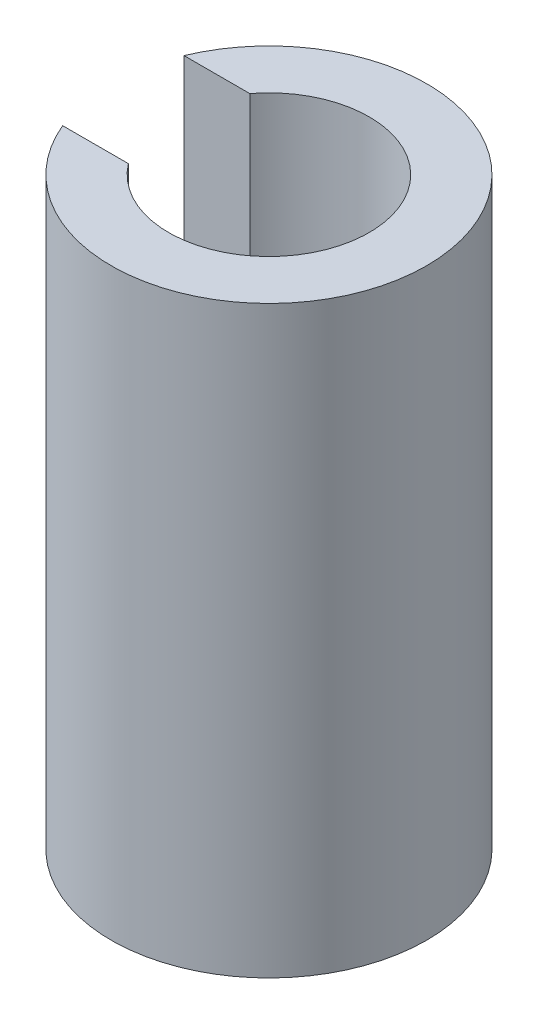
SolidWorks part; units mm, degrees
ref_plane "前基準面" through (0, 0, 0) normal (0, 0, 1) x (1, 0, 0)
ref_plane "上基準面" through (0, 0, 0) normal (0, 1, 0) x (1, 0, 0)
ref_plane "右基準面" through (0, 0, 0) normal (1, 0, 0) x (0, 0, -1)
ref_axis "基準軸1" through (0, -55, 0) along (0, 1, 0)
ref_axis "基準軸2" through (-88.99, 0, 0) along (1, 0, 0)
ref_axis "基準軸3" through (0, 0, 55) along (0, 0, -1)
sketch "草圖1" plane through (0, 0, 0) normal (0, 1, 0) x (1, 0, 0)
  circle A0 centre (0, 0) radius 2.575
  circle A1 centre (0, 0) radius 4.05
  dimension "D1" = 5.15
  dimension "D2" = 8.1
extrude "填料-伸長1" add sketch "草圖1" along normal blind 15
sketch "草圖2" plane through (0, 15, 0) normal (0, 1, 0) x (1, 0, 0)
  line L1 (-4.05, -1.5582) -> (-2.05, -1.5582)
  line L2 (-4.05, -1.5582) -> (-4.05, 1.5582)
  line L3 (-4.05, 1.5582) -> (-2.05, 1.5582)
  line L4 (-2.05, -1.5582) -> (-2.05, 1.5582)
  line L5 (-55, 0) -> (55, 0) construction
  circle A0 centre (0, 0) radius 4.05 construction
  circle A1 centre (0, 0) radius 2.575 construction
  point P4 (-2.05, 0)
  dimension "D1" = 2
extrude "除料-伸長1" cut sketch "草圖2" against normal blind 15
sketch "草圖3" plane through (0, 0, 0) normal (0, -1, 0) x (1, 0, 0)
  line L0 (1.1456, 0.5) -> (2.526, 0.5)
  line L1 (1.1456, -0.5) -> (2.526, -0.5)
  line L2 (4.2835, 0) -> (-4.2835, 0) construction
  arc A0 (1.1456, 0.5) -> (1.1456, -0.5) centre (0, 0) ccw
  arc A1 (-2.05, -1.5582) -> (-2.05, 1.5582) centre (0, 0) ccw construction
  arc A2 (2.526, -0.5) -> (2.526, 0.5) centre (0, 0) ccw
  dimension "D1" = 2.5
  dimension "D2" = 0.5
  dimension "D3" = 0.5
extrude "填料-伸長2" add sketch "草圖3" against normal blind 1 separate body
